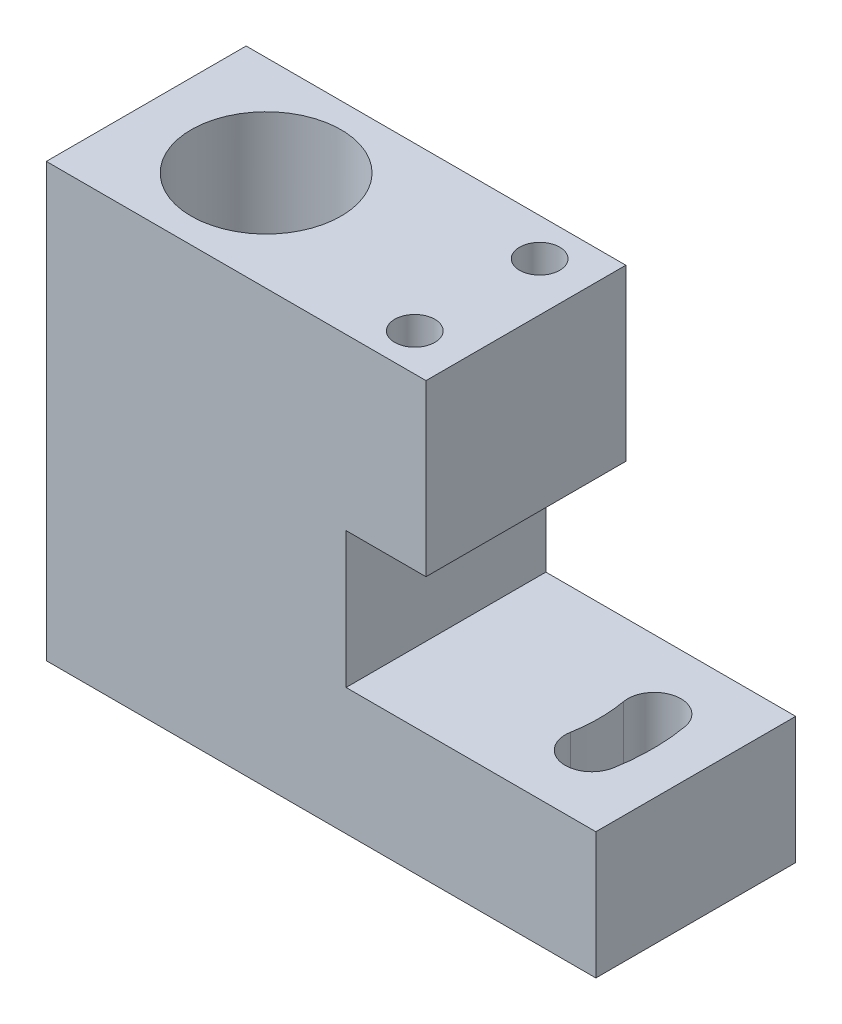
SolidWorks part; units mm, degrees
material "6061 Alloy"
ref_plane "Front Plane" through (0, 0, 0) normal (0, 0, 1) x (1, 0, 0)
ref_plane "Top Plane" through (0, 0, 0) normal (0, 1, 0) x (1, 0, 0)
ref_plane "Right Plane" through (0, 0, 0) normal (1, 0, 0) x (0, 0, -1)
sketch "Sketch1" plane through (0, 0, 0) normal (0, 0, 1) x (1, 0, 0)
  line L2 (-12.7, 54.9656) -> (10.16, 54.9656)
  line L3 (-38.1, 0) -> (31.75, 0)
  line L4 (-38.1, 0) -> (-38.1, 16.1036)
  line L6 (31.75, 0) -> (31.75, 16.1036)
  line L9 (-12.7, 54.9656) -> (-38.1, 54.9656)
  line L10 (-38.1, 16.1036) -> (-38.1, 54.9656)
  line L11 (12.7, 16.1036) -> (31.75, 16.1036)
  line L13 (10.16, 33.3756) -> (0, 33.3756)
  line L14 (10.16, 54.9656) -> (10.16, 33.3756)
  line L15 (12.7, 16.1036) -> (0, 16.1036)
  line L16 (0, 33.3756) -> (0, 16.1036)
  dimension "D3" = 69.85
  dimension "D5" = 16.1036
  dimension "D6" = 17.272
  dimension "D7" = 21.59
  dimension "D8" = 10.16
extrude "Extrude1" add sketch "Sketch1" along normal mid plane 25.4
sketch "Sketch2" plane through (0, 16.1036, 0) normal (0, 1, 0) x (-1, 0, 0)
  line L0 (-22.5127, 3.9696) -> (0, 0) construction
  line L1 (0, 0) -> (-22.5127, -3.9696) construction
  line L2 (0, 0) -> (-22.86, 0) construction
  line L3 (0, 22.86) -> (0, -22.86) construction
  circle A0 centre (-22.86, 0) radius 3.3782 construction
  circle A1 centre (0, 0) radius 22.86 construction
  arc A3 (-25.8396, -4.5562) -> (-19.1858, -3.383) centre (-22.5127, -3.9696) ccw
  arc A4 (-19.1858, 3.383) -> (-25.8396, 4.5562) centre (-22.5127, 3.9696) ccw
  arc A5 (-19.1858, 3.383) -> (-19.1858, -3.383) centre (0, 0) ccw
  arc A6 (-25.8396, 4.5562) -> (-25.8396, -4.5562) centre (0, 0) ccw
  dimension "D2" = 45.72
  dimension "D1" = 6.7564
  dimension "D3" = 20
extrude "Arc mounting slot I" cut sketch "Sketch2" against normal through all
mirror "Arc mounting slot II" about plane through (0, 0, 0) normal (1, 0, 0) of "Arc mounting slot I"
hole_wizard "Clamping screw holes" positions "Sketch5" profile "Sketch4" tap size "1/4-20" standard "Ansi Inch"
sketch "Sketch5" plane through (0, 54.9656, 0) normal (0, 1, 0) x (-1, 0, 0)
  line L0 (0, 0) -> (-3.9688, 0) construction
  line L1 (-3.9688, 7.9375) -> (-3.9688, -7.9375) construction
  point P0 (-3.9688, -7.9375)
  point P1 (-3.9688, 7.9375)
  dimension "D1" = 15.875
  dimension "D2" = 3.9688
cosmetic thread "Hole Thread1" parameters "D1"=15.24, "D2"=6.35
cosmetic thread "Hole Thread2" parameters "D1"=15.24, "D2"=6.35
sketch "Sketch4" plane through (3.9688, 54.9656, -7.9375) normal (1, 0, 0) x (0, 0, 1)
  line L0 (0, 0) -> (0, 23.1238)
  line L1 (0, 23.1238) -> (2.5527, 21.59)
  line L2 (2.5527, 21.59) -> (2.5527, 0)
  line L5 (2.5527, 0) -> (0, 0)
  line L10 (0, 23.1238) -> (-2.5527, 21.59) construction
  line L11 (0, -6.35) -> (0, 107.95) construction
  dimension "Tap Drill Dia." = 5.1054
  dimension "Tap Drill Depth" = 21.59
  dimension "Drill Angle" = 118
sketch "Sketch6" plane through (0, 0, 0) normal (0, 0, 1) x (1, 0, 0)
  line L0 (31.75, 0) -> (31.75, 20.2413) construction
  line L3 (7.9375, 24.0411) -> (0, 24.0411)
  line L4 (7.9375, 24.0411) -> (7.9375, 16.1036)
  line L5 (7.9375, 16.1036) -> (0, 16.1036)
  line L6 (0, 24.0411) -> (0, 16.1036)
  dimension "D1" = 20.2413
  dimension "D2" = 7.9375
sketch "Sketch7" plane through (0, 54.9656, 0) normal (0, 1, 0) x (1, 0, 0)
  circle A0 centre (-22.86, 0) radius 9.525
  dimension "D1" = 19.05
  dimension "D2" = 22.86
extrude "Cut-Extrude1" cut sketch "Sketch7" against normal up to surface (38.862 mm away) up to face at (22.393, 16.1036, 0)
sketch "Sketch8" plane through (-38.1, 0, 0) normal (-1, 0, 0) x (0, 0, 1)
  line L0 (12.7, 54.9656) -> (-12.7, 54.9656) construction
  point P0 (0, 35.9156)
  dimension "D1" = 19.05
hole_wizard "toolrest_set_screw_hole" positions "Sketch9" profile "Sketch10" tap size "1/4-20" standard "ANSI Inch" end condition up to next
sketch "Sketch9" plane through (-38.1, 0, 0) normal (-1, 0, 0) x (0, 0, 1)
  point P0 (0, 35.9156)
sketch "Sketch10" plane through (-38.1, 35.9156, 0) normal (0, 1, 0) x (0, 0, 1)
  line L0 (0, 0) -> (0, 5.715)
  line L1 (0, 5.715) -> (2.5527, 5.715)
  line L2 (2.5527, 5.715) -> (2.5527, 0)
  line L5 (2.5527, 0) -> (0, 0)
  line L11 (0, -6.35) -> (0, 107.95) construction
  dimension "Thru Tap Drill Dia." = 5.1054
  dimension "Thru Tap Drill Depth" = 5.715
cosmetic thread "Hole Thread3" parameters "D2"=6.35
